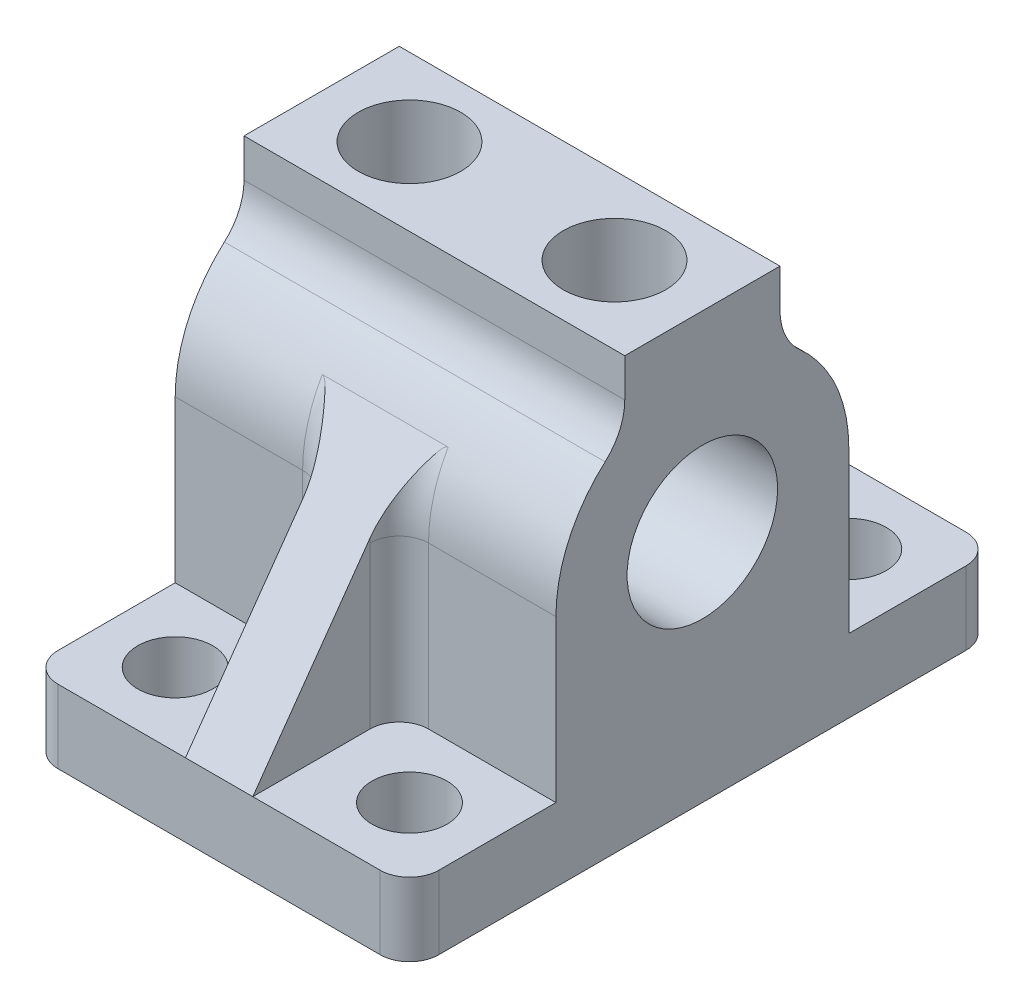
SolidWorks part; units mm, degrees
material "PLA2"
ref_plane "Front Plane" through (0, 0, 0) normal (0, 0, 1) x (1, 0, 0)
ref_plane "Top Plane" through (0, 0, 0) normal (0, 1, 0) x (1, 0, 0)
ref_plane "Right Plane" through (0, 0, 0) normal (1, 0, 0) x (0, 0, -1)
sketch "Sketch1" plane through (0, 0, 0) normal (1, 0, 0) x (0, 0, -1)
  line L0 (0, 0) -> (27506.0917, 0) construction
  line L1 (0.3138, 19.05) -> (27506.4055, 19.05) construction
  line L2 (0, 29.21) -> (0, 0) construction
  line L3 (12.7, 19.05) -> (-12.7, 19.05)
  line L4 (-12.7, 19.05) -> (-12.7, 22.225)
  line L5 (-12.7, 22.225) -> (-6.35, 22.225)
  line L6 (-6.35, 22.225) -> (-6.35, 29.21)
  line L7 (0, 29.21) -> (0, 35.56) construction
  line L8 (6.35, 22.225) -> (6.35, 29.21)
  line L9 (12.7, 22.225) -> (6.35, 22.225)
  line L10 (12.7, 19.05) -> (12.7, 22.225)
  circle A0 centre (0, 29.21) radius 3.2639
  arc A1 (6.35, 29.21) -> (-6.35, 29.21) centre (0, 29.21) ccw
  point P19 (0, 19.05)
  dimension "D2" = 6.5278
  dimension "D4" = 12.7
  dimension "D7" = 3.0861
  dimension "D1" = 19.05
  dimension "D3" = 29.21
  dimension "D5" = 3.175
  dimension "D6" = 6.35
extrude "Boss-Extrude1" add sketch "Sketch1" along normal mid plane 16.51
sketch "Sketch2" plane through (0, 0, 0) normal (1, 0, 0) x (0, 0, -1)
  line L0 (0, 32.4739) -> (0, 25.9461) construction
  line L1 (-5.4993, 32.385) -> (-12.7, 22.225)
  line L2 (-6.35, 22.225) -> (-12.7, 22.225) construction
  line L3 (-12.7, 22.225) -> (-5.4993, 22.225)
  line L4 (-5.4993, 22.225) -> (-5.4993, 32.385)
  line L5 (5.4993, 22.225) -> (5.4993, 32.385)
  line L6 (12.7, 22.225) -> (5.4993, 22.225)
  line L7 (5.4993, 32.385) -> (12.7, 22.225)
  circle A0 centre (0, 29.21) radius 3.2639 construction
  arc A1 (6.35, 29.21) -> (-6.35, 29.21) centre (0, 29.21) ccw construction
  dimension "D1" = 10.16
extrude "Boss-Extrude2" add sketch "Sketch2" along normal mid plane 2.921
sketch "Sketch3" plane through (0, 22.225, 0) normal (0, 1, 0) x (1, 0, 0)
  line L0 (-8.255, 0) -> (8.255, 0) construction
  line L1 (-8.255, 6.35) -> (-8.255, -6.35) construction
  line L2 (8.255, -6.35) -> (8.255, 6.35) construction
  line L3 (0, 12.7) -> (0, -12.7) construction
  line L4 (1.4605, 12.7) -> (-1.4605, 12.7) construction
  line L5 (1.4605, -12.7) -> (-1.4605, -12.7) construction
  circle A0 centre (-5.08, 9.525) radius 1.6256
  circle A1 centre (5.08, 9.525) radius 1.6256
  circle A2 centre (5.08, -9.525) radius 1.6256
  circle A3 centre (-5.08, -9.525) radius 1.6256
  dimension "D1" = 3.2512
  dimension "D2" = 10.16
  dimension "D3" = 19.05
extrude "Cut-Extrude1" cut sketch "Sketch3" against normal through all
sketch "Sketch4" plane through (8.255, 0, 0) normal (1, 0, 0) x (0, 0, -1)
  line L0 (3.3655, 34.5948) -> (-3.3655, 34.5948)
  arc A0 (6.35, 29.21) -> (-6.35, 29.21) centre (0, 29.21) ccw construction
  arc A1 (3.3655, 34.5948) -> (-3.3655, 34.5948) centre (0, 29.21) ccw
  dimension "D1" = 6.731
extrude "Cut-Extrude2" cut sketch "Sketch4" against normal through all
sketch "Sketch6" plane through (0, 34.5948, 0) normal (0, 1, 0) x (1, 0, 0)
  line L4 (8.255, -3.3655) -> (8.255, 3.3655)
  line L5 (8.255, 3.3655) -> (-8.255, 3.3655)
  line L6 (-8.255, 3.3655) -> (-8.255, -3.3655)
  line L7 (-8.255, -3.3655) -> (8.255, -3.3655)
  line L8 (8.255, -3.3655) -> (8.255, 3.3655)
  line L9 (8.255, 3.3655) -> (-8.255, 3.3655)
  line L10 (-8.255, 3.3655) -> (-8.255, -3.3655)
  line L11 (-8.255, -3.3655) -> (8.255, -3.3655)
  dimension "D1" = 0
extrude "Boss-Extrude3" add sketch "Sketch6" along normal blind 2.921
sketch "Sketch5" plane through (0, 37.5158, 0) normal (0, 1, 0) x (1, 0, 0)
  line L0 (0, 12.7) -> (0, -12.7) construction
  line L1 (1.4605, 12.7) -> (-1.4605, 12.7) construction
  line L2 (1.4605, -12.7) -> (-1.4605, -12.7) construction
  line L3 (-8.255, 0) -> (8.255, 0) construction
  line L6 (-8.255, 3.3655) -> (-8.255, -3.3655) construction
  line L7 (8.255, -3.3655) -> (8.255, 3.3655) construction
  circle A0 centre (-4.445, 0) radius 2.2225
  circle A1 centre (4.445, 0) radius 2.2225
  dimension "D1" = 4.445
  dimension "D2" = 8.89
extrude "Cut-Extrude3" cut sketch "Sketch5" against normal blind 6.35
fillet "Fillet1" radius 1.27 12 edges at (-1.4605, 30.8535, 6.1336) (1.4605, 30.8535, 6.1336) (-1.4605, 30.8535, -6.1336) (1.4605, 30.8535, -6.1336) (-1.4605, 25.7175, 6.35) (1.4605, 25.7175, 6.35) (-1.4605, 25.7175, -6.35) (1.4605, 25.7175, -6.35) (-8.255, 20.6375, -12.7) (8.255, 20.6375, -12.7) (-8.255, 20.6375, 12.7) (8.255, 20.6375, 12.7)
fillet "Fillet2" radius 2.54 2 edges at (0, 34.5948, -3.3655) (0, 34.5948, 3.3655)
